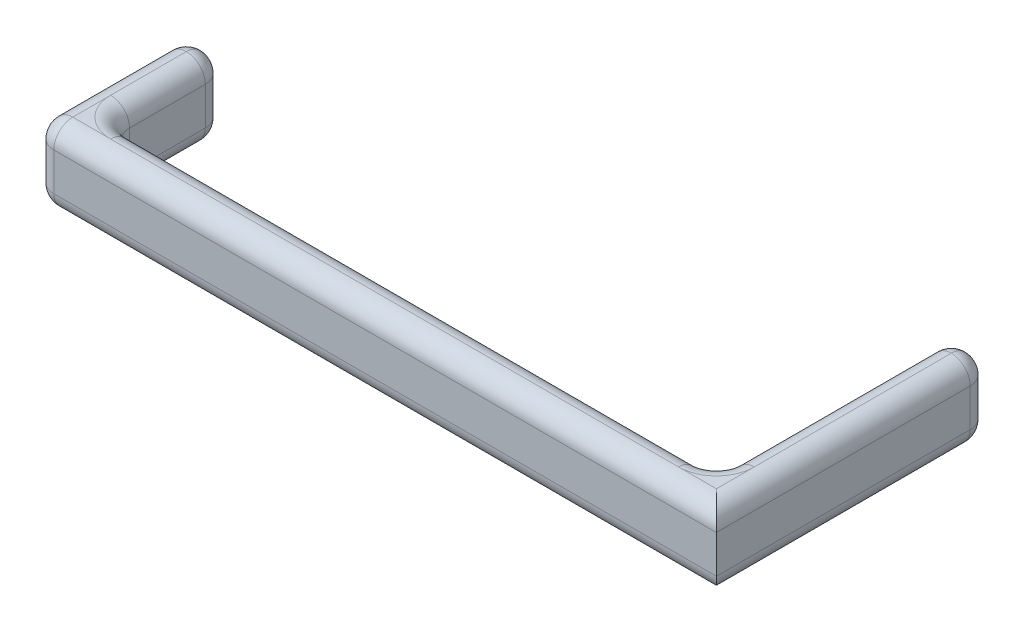
SolidWorks part; units mm, degrees
ref_plane "Front Plane" through (0, 0, 0) normal (0, 0, 1) x (1, 0, 0)
ref_plane "Top Plane" through (0, 0, 0) normal (0, 1, 0) x (1, 0, 0)
ref_plane "Right Plane" through (0, 0, 0) normal (1, 0, 0) x (0, 0, -1)
sketch "Sketch1" plane through (0, 0, 0) normal (0, 0, 1) x (1, 0, 0)
  line L1 (0, 0) -> (-812.8, 0)
  line L2 (0, 0) -> (0, 101.6)
  line L3 (0, 101.6) -> (-812.8, 101.6)
  line L4 (-812.8, 0) -> (-812.8, 101.6)
  dimension "D1" = 101.6
  dimension "D2" = 812.8
extrude "Boss-Extrude1" add sketch "Sketch1" along normal blind 50.8
sketch "Sketch2" plane through (0, 0, 50.8) normal (0, 0, 1) x (1, 0, 0)
  line L0 (0, 101.6) -> (-812.8, 101.6) construction
  line L1 (-812.8, 0) -> (-863.6, 0)
  line L2 (-812.8, 0) -> (-812.8, 101.6)
  line L3 (-812.8, 101.6) -> (-863.6, 101.6)
  line L4 (-863.6, 0) -> (-863.6, 101.6)
  line L5 (0, 101.6) -> (50.8, 101.6)
  line L6 (0, 101.6) -> (0, 0)
  line L7 (0, 0) -> (50.8, 0)
  line L8 (50.8, 101.6) -> (50.8, 0)
  dimension "D1" = 50.8
  dimension "D2" = 50.8
extrude "Boss-Extrude2" add sketch "Sketch2" against normal blind 203.2
sketch "Sketch6" plane through (50.8, 0, 0) normal (1, 0, 0) x (0, 0, -1)
  line L0 (152.4, 0) -> (-50.8, 0) construction
  line L1 (-50.8, 101.6) -> (315.087, 101.6)
  line L2 (-50.8, 101.6) -> (-50.8, 0)
  line L3 (-50.8, 0) -> (315.087, 0)
  line L4 (315.087, 101.6) -> (315.087, 0)
  dimension "D1" = 365.887
  dimension "D2" = 0
extrude "Boss-Extrude4" add sketch "Sketch6" against normal up to surface (50.8 mm away) up to face at (0, 50.8, -76.2)
fillet "Fillet2" radius 25.4 19 edges at (-406.4, 0, 50.8) (50.8, 0, -132.1435) (-406.4, 0, 0) (-863.6, 0, -50.8) (-863.6, 50.8, 50.8) (-863.6, 50.8, -152.4) (0, 50.8, -315.087) (50.8, 50.8, -315.087) (0, 50.8, 0) (0, 0, -157.5435) (-812.8, 50.8, -152.4) (-812.8, 0, -76.2) (-812.8, 50.8, 0) (-812.8, 101.6, -76.2) (-406.4, 101.6, 0) (0, 101.6, -157.5435) (50.8, 101.6, -132.1435) (-406.4, 101.6, 50.8) (-863.6, 101.6, -50.8)
